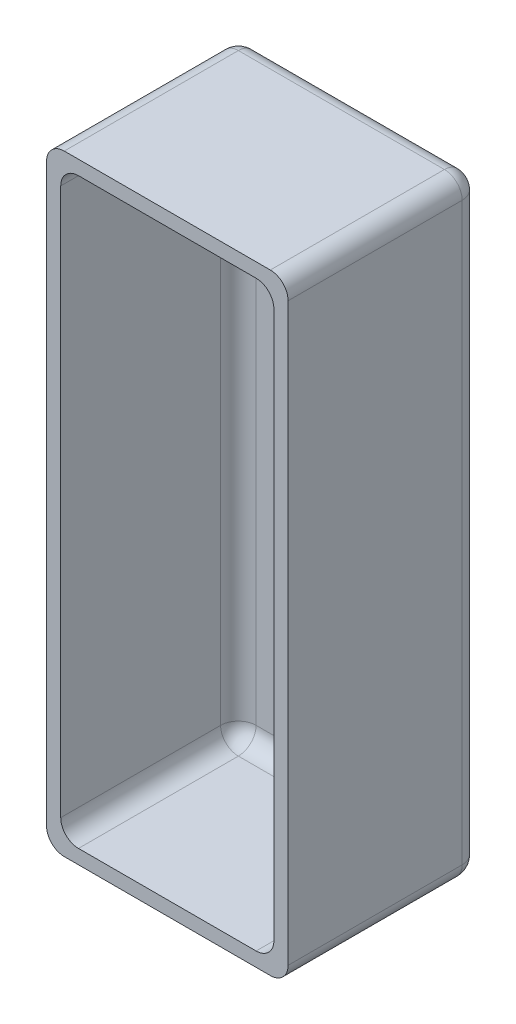
SolidWorks part; units mm, degrees
ref_plane "Plan de face" through (0, 0, 0) normal (0, 0, 1) x (1, 0, 0)
ref_plane "Plan de dessus" through (0, 0, 0) normal (0, 1, 0) x (1, 0, 0)
ref_plane "Plan de droite" through (0, 0, 0) normal (1, 0, 0) x (0, 0, -1)
sketch "Esquisse1" plane through (0, 0, 0) normal (0, 0, 1) x (1, 0, 0)
  line L1 (15, -41) -> (-15, -41)
  line L2 (15, -41) -> (15, 41)
  line L3 (15, 41) -> (-15, 41)
  line L4 (-15, -41) -> (-15, 41)
  line L5 (15, -41) -> (-15, 41) construction
  line L6 (15, 41) -> (-15, -41) construction
  point P0 (0, 0)
  dimension "D1" = 30
  dimension "D2" = 82
extrude "Boss.-Extru.1" add sketch "Esquisse1" along normal blind 25
shell "Coque1" thickness 2 removed face at (0, 0, 25) outward yes
fillet "Congé1" radius 2.5 16 edges at (0, 43, -2) (-17, 0, -2) (0, -43, -2) (17, 0, -2) (-17, 43, 11.5) (17, 43, 11.5) (-17, -43, 11.5) (17, -43, 11.5) (-15, -41, 12.5) (0, -41, 0) (15, -41, 12.5) (-15, 0, 0) (15, 0, 0) (0, 41, 0) (-15, 41, 12.5) (15, 41, 12.5)
